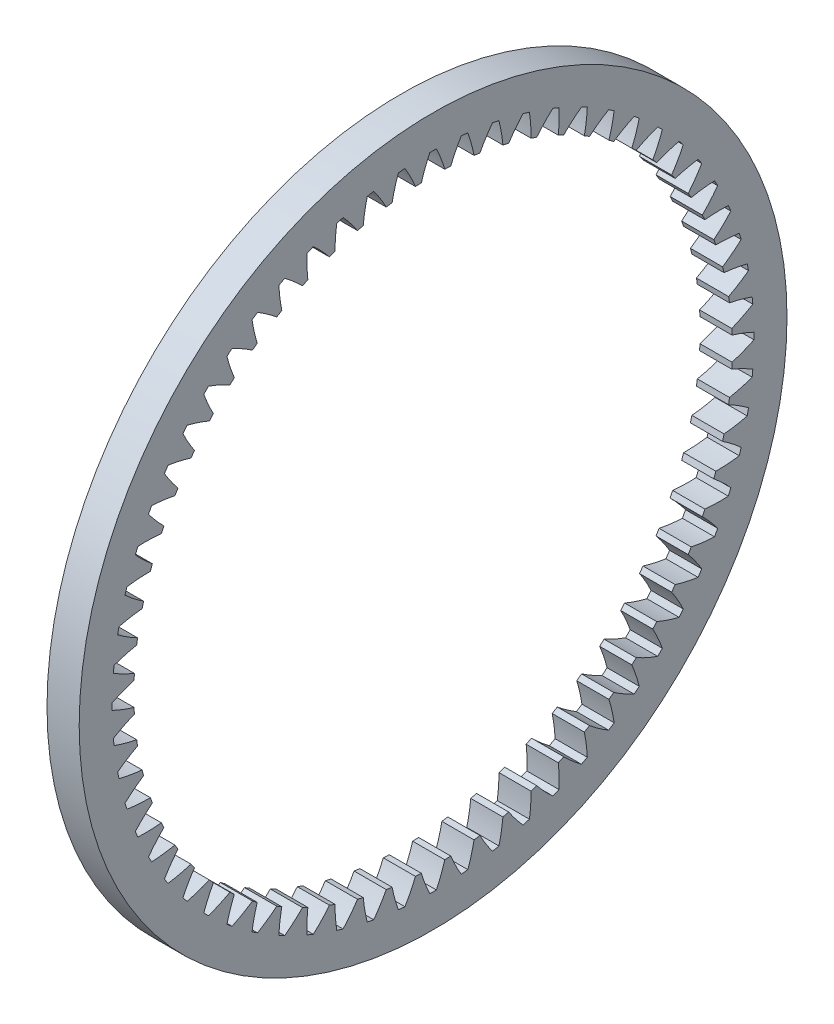
SolidWorks part; units mm, degrees
ref_plane "Plane1" through (0, 0, 0) normal (0, 0, 1) x (1, 0, 0)
ref_plane "Plane2" through (0, 0, 0) normal (0, 1, 0) x (1, 0, 0)
ref_plane "Plane3" through (0, 0, 0) normal (1, 0, 0) x (0, 0, -1)
other "Configuration Table"
sketch "HoldingSke" plane through (0, 0, 0) normal (0, 1, 0) x (1, 0, 0)
  line L0 (0, 0) -> (0.1461, -0.2996)
  line L1 (-15, 0) -> (100, 0) construction
  line L2 (0, 0) -> (-2.1039, 2.3779)
  line L3 (0, 0) -> (-11.863, 4.5341)
  line L4 (0, 0) -> (3.7858, 7.762)
  line L5 (0, 0) -> (-23.7986, -8.8762)
  line L6 (0, 0) -> (-10.5278, -7.1032)
  line L7 (-2.1039, 2.3779) -> (3.3635, 27.1825)
  line L8 (-76.2, 5.3779) -> (-54.61, 5.3779)
  line L9 (-71.009, 38.7566) -> (-53.1078, 45.2721)
  line L10 (-76.2, 71.12) -> (104.1128, 71.12)
  line L11 (0, 0) -> (-10, 0)
  line L12 (-76.2, 101.6) -> (-76.093, 101.6)
  line L13 (24.9733, 27.94) -> (52.9518, 28.4284)
  line L14 (24.9733, 27.94) -> (24.9743, 27.94)
  line L15 (24.9733, 27.94) -> (100.4006, 29.5858)
  circle A0 centre (0, 0) radius 110
  circle A1 centre (0, 0) radius 12.7
  circle A2 centre (0, 0) radius 12.7
  dimension "Num_teeth" = 64
  dimension "Pitch_radius" = 180.3128
  dimension "Width" = 10
  dimension "Diameter" = 220
sketch "BasProSke" plane through (0, 0, 0) normal (0, 1, 0) x (1, 0, 0)
  line L0 (-10, 0) -> (60, 0) construction
  line L1 (0, 93) -> (0, 110)
  line L2 (0, 93) -> (10, 93)
  line L3 (10, 93) -> (10, 110)
  line L4 (10, 110) -> (0, 110)
  dimension "Thickness" = 10
  dimension "Diameter" = 220
revolve "Base-Revolve" add sketch "BasProSke" angle 360 about L0
sketch "TooCutSke" plane through (0, 0, 0) normal (1, 0, 0) x (0, 0, -1)
  line L3 (2.6235, 95.9641) -> (2.6235, 53.6633) construction
  line L4 (0, 0) -> (0, 59.563) construction
  line L5 (0, 0) -> (-3.3527, 68.2452) construction
  line L6 (-42.3563, 79.2065) -> (33.8134, 82.9485) construction
  circle A0 centre (0, 0) radius 96 construction
  circle A1 centre (0, 0) radius 99.751 construction
  circle A2 centre (0, 0) radius 81.1894 construction
  circle A3 centre (0, 0) radius 92.9746 construction
  arc A4 (3.6481, 92.903) -> (1.0273, 99.7457) centre (-42.3563, 79.2065) ccw
  arc A5 (3.6481, 92.903) -> (-3.6481, 92.903) centre (0, 0) ccw
  arc A6 (1.0273, 99.7457) -> (-1.0273, 99.7457) centre (0, 0) ccw
  arc A7 (-1.0273, 99.7457) -> (-3.6481, 92.903) centre (42.3563, 79.2065) ccw
extrude "ToothCut" cut sketch "TooCutSke" along normal through all
fillet "Breaks" [suppressed] radius 0.3
fillet "RootFillets" [suppressed] radius 0.751
pattern_circular "TeethCuts" count 64 every 5.625 about axis through (-10, 0, 0) along (1, 0, 0) of "RootFillets", "Breaks", "ToothCut"
equation "' \"Module@HoldingSke\" = 6.35"
equation "' \"Num_teeth@HoldingSke\" = 24"
equation "' \"Ap@HoldingSke\" =  14.5"
equation "' \"Ap@HoldingSke\" = 14.5"
equation "' \"Width@HoldingSke\" = 12"
equation "' \"Diameter@HoldingSke\" = 8 * 25.4"
equation "' \"Show_teeth@HoldingSke\" = 100"
equation "' \"Backlash@HoldingSke\" = 0.009 * 25.4"
equation "' \"Addendum_fac@HoldingSke\" = 1.0"
equation "' \"Dedendum_fac@HoldingSke\" = 1.25"
equation "' \"Dedendum_add@HoldingSke\" = 0.00005 * 25.4"
equation "' \"Clearance_fac@HoldingSke\" = 0.25"
equation "\"Pitch@HoldingSke\" = 1 / \"Module@HoldingSke\" "
equation "\"Overcut_dia@TooCutSke\" = (\"Num_teeth@HoldingSke\" - 2 * \"Addendum_fac@HoldingSke\") / \"Pitch@HoldingSke\" - 0.002 * 25.4"
equation "\"Pitch_dia@TooCutSke\" = \"Num_teeth@HoldingSke\" / \"Pitch@HoldingSke\""
equation "\"Base_dia@TooCutSke\" = \"Num_teeth@HoldingSke\" / \"Pitch@HoldingSke\" * cos((\"Ap@HoldingSke\"  * 3.14159265 / 180)) * 0.90"
equation "\"Root_dia@TooCutSke\" = \"Num_teeth@HoldingSke\"  / \"Pitch@HoldingSke\" + 2 *  \"Dedendum_fac@HoldingSke\"/ \"Pitch@HoldingSke\" + \"Dedendum_add@HoldingSke\" * 2"
equation "\"Half_ang@TooCutSke\" = 180 / \"Num_teeth@HoldingSke\""
equation "\"Half_CT@TooCutSke\" = \"Num_teeth@HoldingSke\" / \"Pitch@HoldingSke\" * sin((3.14159265 / 2 / \"Num_teeth@HoldingSke\")) / 2 + 10 * \"Backlash@HoldingSke\" / 4"
equation "\"Flank_rad@TooCutSke\" = \"Num_teeth@HoldingSke\" / \"Pitch@HoldingSke\" / 4"
equation "\"Radius@RootFillets\"= \"Clearance_fac@HoldingSke\" / \"Pitch@HoldingSke\" + \"Dedendum_add@HoldingSke\""
equation "\"Break_rad@Breaks\" = 0.02 / \"Pitch@HoldingSke\" * 5"
equation "\"Num_teeth@TeethCuts\" = int( \"Show_teeth@HoldingSke\" ) + 1"
equation "\"Num_teeth@TeethCuts\" = ((sgn( \"Num_teeth@TeethCuts\" - \"Num_teeth@HoldingSke\" )-1)*( \"Num_teeth@TeethCuts\" - \"Num_teeth@HoldingSke\" ))/-2+ \"Num_teeth@HoldingSke\""
equation "\"Num_teeth@TeethCuts\" = ((sgn( \"Num_teeth@TeethCuts\" - 2.0)+1)*( \"Num_teeth@TeethCuts\" - 2.0))/2 +2.0"
equation "\"Angle@TeethCuts\" = 360.0 / \"Num_teeth@HoldingSke\""
equation "\"Diameter@BasProSke\" = \"Num_teeth@HoldingSke\"  / \"Pitch@HoldingSke\" + 2 *  \"Dedendum_fac@HoldingSke\"/ \"Pitch@HoldingSke\" + \"Dedendum_add@HoldingSke\" * 2 + 0.002 * 25.4"
equation "\"Diameter@BasProSke\" = ((sgn( \"Diameter@BasProSke\"  - \"Diameter@HoldingSke\" )+1)*( \"Diameter@BasProSke\"  - \"Diameter@HoldingSke\" ))/2 + \"Diameter@HoldingSke\""
equation "\"Inside_diameter@BasProSke\" =  (\"Num_teeth@HoldingSke\" - 2 * \"Addendum_fac@HoldingSke\") / \"Pitch@HoldingSke\" "
equation "\"Thickness@BasProSke\"  = \"Width@HoldingSke\""
